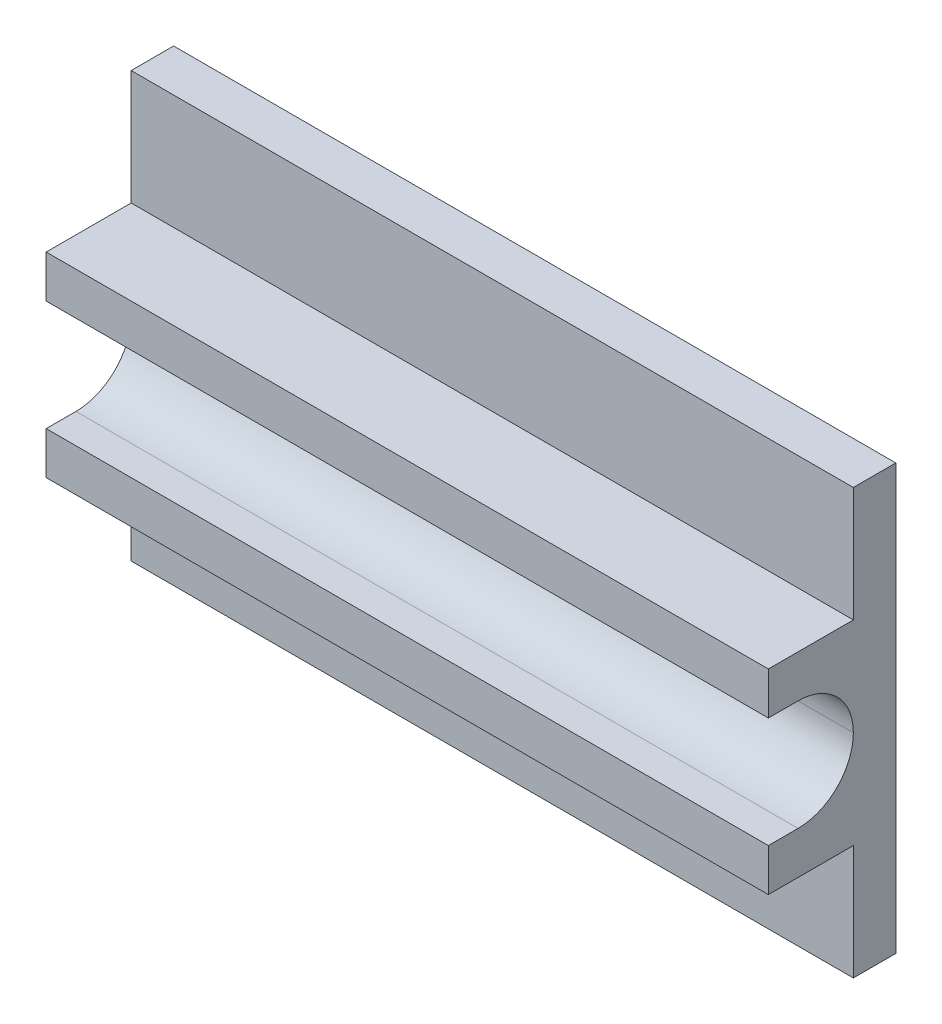
SolidWorks part; units mm, degrees
ref_plane "Спереди" through (0, 0, 0) normal (0, 0, 1) x (1, 0, 0)
ref_plane "Сверху" through (0, 0, 0) normal (0, 1, 0) x (1, 0, 0)
ref_plane "Справа" through (0, 0, 0) normal (1, 0, 0) x (0, 0, -1)
sketch "Skizze1" plane through (0, 0, 0) normal (0, 0, 1) x (1, 0, 0)
  line L1 (-10, 5) -> (7, 5)
  line L2 (-10, 5) -> (-10, -5)
  line L3 (-10, -5) -> (7, -5)
  line L4 (7, 5) -> (7, -5)
  dimension "D1" = 10
  dimension "D2" = 17
  dimension "D3" = 10
  dimension "D4" = 5
extrude "Aufsatz-Linear austragen1" add sketch "Skizze1" along normal blind 1
sketch "Skizze2" plane through (0, 0, 1) normal (0, 0, 1) x (1, 0, 0)
  line L0 (-10, 5) -> (-10, -5) construction
  line L1 (-10, 2.3) -> (7, 2.3)
  line L2 (-10, 2.3) -> (-10, 1.3)
  line L3 (-10, 1.3) -> (7, 1.3)
  line L4 (7, 2.3) -> (7, 1.3)
  line L5 (7, -5) -> (7, 5) construction
  line L6 (7, 5) -> (-10, 5) construction
  line L7 (-10, -1.3) -> (7, -1.3)
  line L8 (-10, -1.3) -> (-10, -2.3)
  line L9 (-10, -2.3) -> (7, -2.3)
  line L10 (7, -1.3) -> (7, -2.3)
  line L11 (-10, -5) -> (7, -5) construction
  dimension "D1" = 1
  dimension "D2" = 1
  dimension "D3" = 2.7
  dimension "D4" = 2.7
extrude "Aufsatz-Linear austragen2" add sketch "Skizze2" along normal blind 2
fillet "Verrundung1" radius 1.3 2 edges at (-1.5, -1.3, 1) (-1.5, 1.3, 1)
